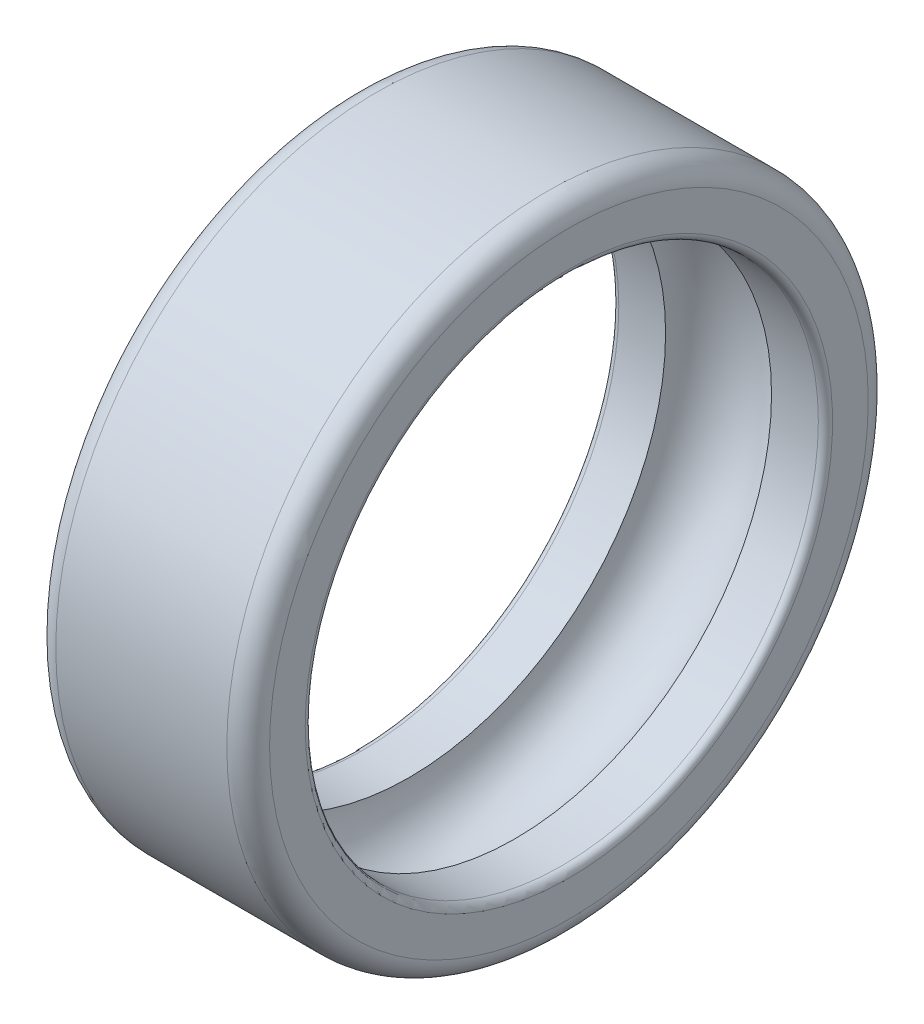
SolidWorks part; units mm, degrees
material "Plain Carbon Steel"
ref_plane "Front Plane" through (0, 0, 0) normal (0, 0, 1) x (1, 0, 0)
ref_plane "Top Plane" through (0, 0, 0) normal (0, 1, 0) x (1, 0, 0)
ref_plane "Right Plane" through (0, 0, 0) normal (1, 0, 0) x (0, 0, -1)
ref_plane "Plane1" through (0, 0, 0) normal (0, 0, -1) x (-1, 0, 0)
sketch "Sketch1" plane through (0, 0, 0) normal (0, 0, -1) x (-1, 0, 0)
  line L0 (-6.9, 16.65) -> (-6.2433, 16.65)
  line L1 (-4.7567, 16.65) -> (-4.1, 16.65)
  line L2 (-4, 16.75) -> (-4, 17.25)
  line L3 (-4.3, 17.55) -> (-6.7, 17.55)
  line L4 (-7, 17.25) -> (-7, 16.75)
  line L5 (-8.0514, 13.05) -> (-2.9486, 13.05) construction
  line L6 (-5.5, 16.55) -> (-5.5, 13.05) construction
  arc A0 (-6.2433, 16.65) -> (-4.7567, 16.65) centre (-5.5, 16.55) cw
  arc A1 (-4.1, 16.65) -> (-4, 16.75) centre (-4.1, 16.75) ccw
  arc A2 (-4, 17.25) -> (-4.3, 17.55) centre (-4.3, 17.25) ccw
  arc A3 (-6.7, 17.55) -> (-7, 17.25) centre (-6.7, 17.25) ccw
  arc A4 (-7, 16.75) -> (-6.9, 16.65) centre (-6.9, 16.75) ccw
  dimension "D3" = 0.75
  dimension "D1" = 9
  dimension "D2" = 7.2
  dimension "D4" = 3
  dimension "D5" = 7
revolve "Revolve1" add sketch "Sketch1" angle 360 about L5 reverse direction yes
